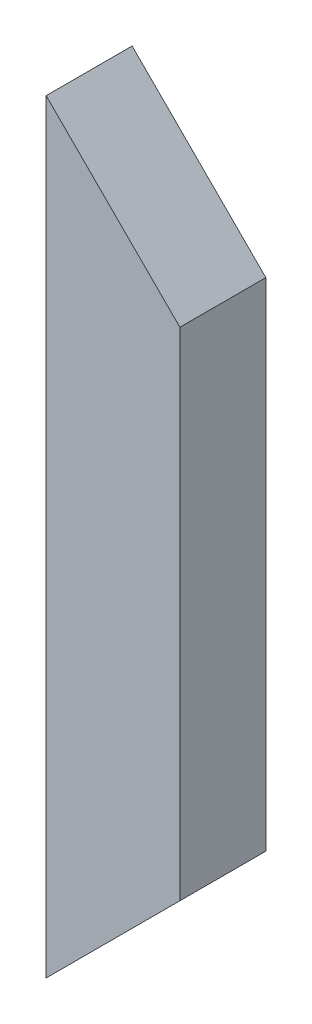
SolidWorks part; units mm, degrees
ref_plane "Front Plane" through (0, 0, 0) normal (0, 0, 1) x (1, 0, 0)
ref_plane "Top Plane" through (0, 0, 0) normal (0, 1, 0) x (1, 0, 0)
ref_plane "Right Plane" through (0, 0, 0) normal (1, 0, 0) x (0, 0, -1)
sketch "Sketch1" plane through (0, 0, 0) normal (0, 1, 0) x (1, 0, 0)
  line L1 (-35, 22.5) -> (35, 22.5)
  line L2 (-35, 22.5) -> (-35, -22.5)
  line L3 (-35, -22.5) -> (35, -22.5)
  line L4 (35, 22.5) -> (35, -22.5)
  line L5 (-35, 22.5) -> (35, -22.5) construction
  line L6 (-35, -22.5) -> (35, 22.5) construction
  point P0 (0, 0)
  dimension "D1" = 45
  dimension "D2" = 70
extrude "Shape" add sketch "Sketch1" along normal blind 400
sketch "Sketch2" plane through (0, 0, 22.5) normal (0, 0, 1) x (1, 0, 0)
  line L0 (-35, 400) -> (35, 330)
  line L1 (35, 400) -> (35, 0) construction
  line L2 (-35, 400) -> (35, 400) construction
  line L3 (35, 200) -> (-35, 200) construction
  line L4 (-35, 0) -> (35, 70)
  line L7 (-35, 0) -> (35, 0)
  line L8 (35, 0) -> (35, 400)
  line L9 (35, 400) -> (-35, 400)
  line L10 (-35, 400) -> (-35, 0)
  line L11 (-35, 0) -> (35, 0)
  line L12 (35, 0) -> (35, 400)
  line L13 (35, 400) -> (-35, 400)
  line L14 (-35, 400) -> (-35, 0)
  line M7 (-35, 0) -> (35, 0)
  line M8 (35, 0) -> (35, 400)
  line M9 (35, 400) -> (-35, 400)
  dimension "D1" = 45
  dimension "D2" = 0
extrude "Cut-Extrude1" cut sketch "Sketch2" against normal up to next contours L0 M9 M8 | L4 M7 M8 region at (11.6667, 376.6667, 22.5) region at (11.6667, 23.3333, 22.5)
